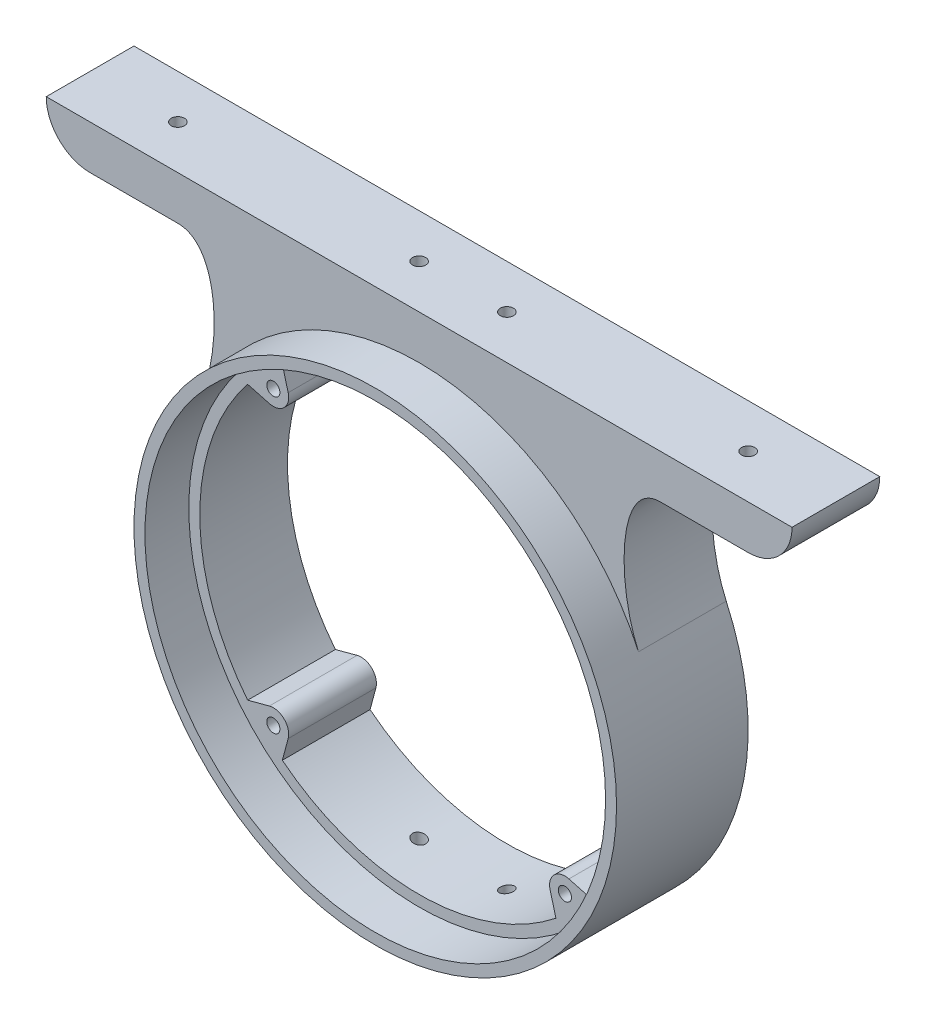
SolidWorks part; units mm, degrees
ref_plane "前视基准面" through (0, 0, 0) normal (0, 0, 1) x (1, 0, 0)
ref_plane "上视基准面" through (0, 0, 0) normal (0, 1, 0) x (1, 0, 0)
ref_plane "右视基准面" through (0, 0, 0) normal (1, 0, 0) x (0, 0, -1)
sketch "草图2" plane through (0, 0, 0) normal (0, 0, 1) x (1, 0, 0)
  line L0 (0, 55) -> (37.8067, 55) construction
  line L1 (-55, 0) -> (-55, 32.093) construction
  line L2 (-45, 109.1596) -> (-45, 87.8343) construction
  line L3 (-55, 55) -> (-85, 55) construction
  line L4 (-85, 55) -> (-85, 65) construction
  line L5 (-75, 55) -> (-55, 55)
  line L6 (0, 104.3034) -> (0, 77.4884) construction
  line L7 (85, 55) -> (85, 65) construction
  line L8 (55, 55) -> (85, 55) construction
  line L9 (75, 55) -> (55, 55)
  line L10 (-85, 65) -> (85, 65)
  line L13 (-50, 22.9129) -> (-45, 33.8238) construction
  line L14 (-45, 33.8238) -> (-45, 55) construction
  line L15 (-45, 55) -> (-55, 55) construction
  line L16 (50, 22.9129) -> (45, 33.8238) construction
  line L17 (45, 33.8238) -> (45, 55) construction
  line L18 (45, 55) -> (55, 55) construction
  circle A1 centre (0, 0) radius 55 construction
  arc A2 (-85, 65) -> (-75, 55) centre (-75, 65) ccw
  arc A3 (85, 65) -> (75, 55) centre (75, 65) cw
  arc A4 (-50, 22.9129) -> (50, 22.9129) centre (0, 0) ccw
  circle A7 centre (0, 0) radius 50
  spline S0 degree 3 poles (-50, 22.9129) (-45, 33.8238) (-45, 55) (-55, 55) knots 0 0 0 0 1 1 1 1
  spline S1 degree 3 poles (50, 22.9129) (45, 33.8238) (45, 55) (55, 55) knots 0 0 0 0 1 1 1 1
  dimension "D1" = 110
  dimension "D2" = 100
  dimension "D3" = 10
  dimension "D5" = 10
  dimension "D4" = 30
  dimension "D8" = 5
extrude "凸台-拉伸1" add sketch "草图2" along normal blind 20
sketch "草图3" plane through (0, 65, 0) normal (0, 1, 0) x (1, 0, 0)
  line L0 (0, 0) -> (0, -20) construction
  line L2 (-85, -10) -> (-55.1419, -10) construction
  line L4 (-85, -20) -> (-85, 0) construction
  circle A0 centre (-65, -10) radius 1.5
  circle A1 centre (-10, -10) radius 1.5
  circle A2 centre (10, -10) radius 1.5
  circle A3 centre (65, -10) radius 1.5
  point P5 (-85, -10)
  dimension "D1" = 3
  dimension "D2" = 10
  dimension "D3" = 55
extrude "切除-拉伸1" cut sketch "草图3" against normal through all
sketch "草图4" plane through (0, 0, 0) normal (0, 0, 1) x (1, 0, 0)
  line L0 (0, 0) -> (-21.2173, 21.2173) construction
  line L1 (-31.1791, 39.0879) -> (-29.8533, 34.1399)
  line L2 (-39.0879, 31.1791) -> (-34.1399, 29.8533)
  line L3 (0, 0) -> (0, 13.1846) construction
  line L6 (31.1791, 39.0879) -> (29.8533, 34.1399)
  line L7 (39.0879, 31.1791) -> (34.1399, 29.8533)
  line L8 (39.0879, -31.1791) -> (34.1399, -29.8533)
  line L9 (31.1791, -39.0879) -> (29.8533, -34.1399)
  line L10 (-31.1791, -39.0879) -> (-29.8533, -34.1399)
  line L11 (-39.0879, -31.1791) -> (-34.1399, -29.8533)
  line L12 (0, 0) -> (-74.7871, 0) construction
  circle A0 centre (-33.234, 33.234) radius 1.5
  arc A2 (-29.8533, 34.1399) -> (-34.1399, 29.8533) centre (-33.234, 33.234) cw
  arc A3 (-31.1791, 39.0879) -> (-39.0879, 31.1791) centre (0, 0) ccw
  circle A7 centre (0, 0) radius 50 construction
  arc A8 (34.1399, 29.8533) -> (29.8533, 34.1399) centre (33.234, 33.234) cw
  arc A9 (39.0879, 31.1791) -> (31.1791, 39.0879) centre (0, 0) ccw
  circle A10 centre (33.234, 33.234) radius 1.5
  arc A11 (29.8533, -34.1399) -> (34.1399, -29.8533) centre (33.234, -33.234) cw
  arc A12 (31.1791, -39.0879) -> (39.0879, -31.1791) centre (0, 0) ccw
  circle A13 centre (33.234, -33.234) radius 1.5
  arc A14 (-34.1399, -29.8533) -> (-29.8533, -34.1399) centre (-33.234, -33.234) cw
  arc A15 (-39.0879, -31.1791) -> (-31.1791, -39.0879) centre (0, 0) ccw
  circle A16 centre (-33.234, -33.234) radius 1.5
  point P35 (0, 0)
  dimension "D1" = 30
  dimension "D2" = 2
  dimension "D3" = 3
  dimension "D5" = 4
  dimension "D4" = 47
  dimension "D6" = 45
extrude "凸台-拉伸2" add sketch "草图4" along normal through all
sketch "草图6" plane through (0, 0, 0) normal (0, 1, 0) x (1, 0, 0)
  line L0 (85, 0) -> (-85, 0) construction
  line L1 (-8.4123, -7.25) -> (-11.5877, -7.25)
  line L2 (-11.5877, -7.25) -> (-13.1754, -10)
  line L3 (-13.1754, -10) -> (-11.5877, -12.75)
  line L4 (-11.5877, -12.75) -> (-8.4123, -12.75)
  line L5 (-8.4123, -12.75) -> (-6.8246, -10)
  line L6 (-6.8246, -10) -> (-8.4123, -7.25)
  line L7 (0, 0) -> (0, -20) construction
  line L8 (85, -20) -> (-85, -20) construction
  line L9 (6.8246, -10) -> (8.4123, -7.25)
  line L10 (8.4123, -12.75) -> (6.8246, -10)
  line L11 (11.5877, -12.75) -> (8.4123, -12.75)
  line L12 (13.1754, -10) -> (11.5877, -12.75)
  line L13 (11.5877, -7.25) -> (13.1754, -10)
  line L14 (8.4123, -7.25) -> (11.5877, -7.25)
  circle A0 centre (-10, -10) radius 2.75 construction
  circle A1 centre (10, -10) radius 2.75 construction
  point P11 (-12.3816, -11.375)
  dimension "D1" = 5.5
extrude "切除-拉伸4" cut sketch "草图6" against normal through all from offset 52 offset against normal yes
sketch "草图7" plane through (0, 55, 0) normal (0, -1, 0) x (1, 0, 0)
  line L0 (-75, 20) -> (-55, 20) construction
  line L1 (-63.4123, 12.75) -> (-66.5877, 12.75)
  line L2 (-66.5877, 12.75) -> (-68.1754, 10)
  line L3 (-68.1754, 10) -> (-66.5877, 7.25)
  line L4 (-66.5877, 7.25) -> (-63.4123, 7.25)
  line L5 (-63.4123, 7.25) -> (-61.8246, 10)
  line L6 (-61.8246, 10) -> (-63.4123, 12.75)
  line L7 (0, 0) -> (0, 40.9385) construction
  line L9 (61.8246, 10) -> (63.4123, 12.75)
  line L10 (63.4123, 7.25) -> (61.8246, 10)
  line L11 (66.5877, 7.25) -> (63.4123, 7.25)
  line L12 (68.1754, 10) -> (66.5877, 7.25)
  line L13 (66.5877, 12.75) -> (68.1754, 10)
  line L14 (63.4123, 12.75) -> (66.5877, 12.75)
  circle A0 centre (-65, 10) radius 2.75 construction
  circle A1 centre (65, 10) radius 2.75 construction
  dimension "D1" = 5.5
extrude "切除-拉伸5" cut sketch "草图7" against normal blind 2
sketch "草图9" plane through (0, 0, 20) normal (0, 0, 1) x (1, 0, 0)
  circle A0 centre (0, 0) radius 50
  circle A1 centre (0, 0) radius 55
extrude "凸台-拉伸3" add sketch "草图9" along normal blind 10
sketch "草图10" plane through (0, 0, 30) normal (0, 0, 1) x (1, 0, 0)
  circle A0 centre (0, 0) radius 50
  circle A1 centre (0, 0) radius 52.5
  circle A2 centre (0, 0) radius 50 construction
  dimension "D1" = 2.5
extrude "切除-拉伸6" cut sketch "草图10" against normal blind 10
